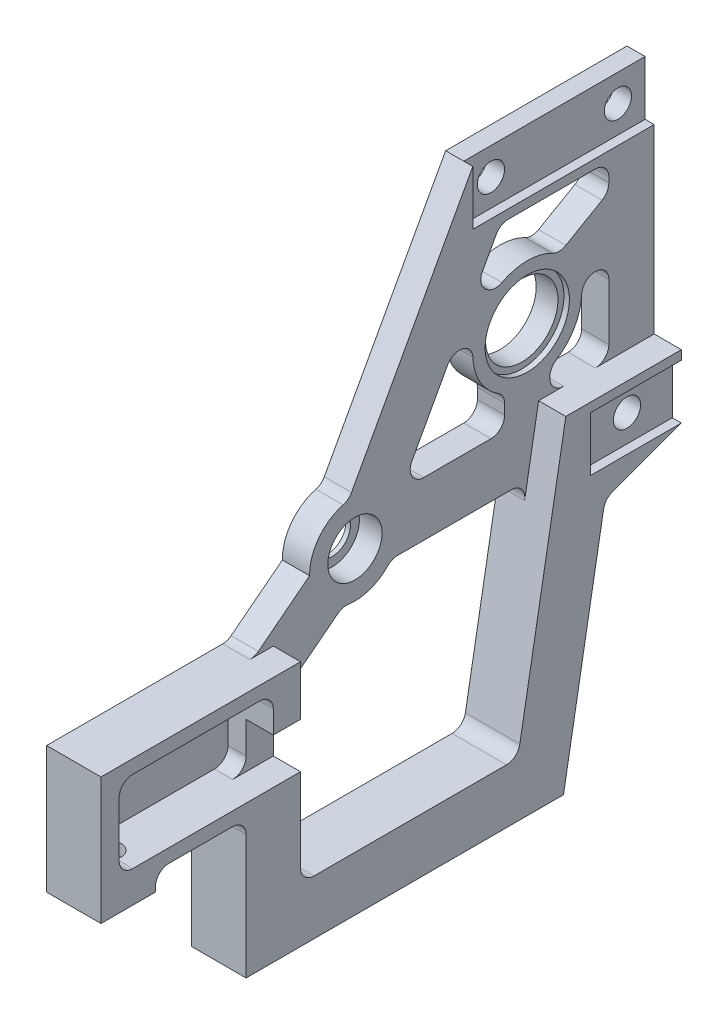
SolidWorks part; units mm, degrees
material "1060 Alloy"
ref_plane "Front Plane" through (0, 0, 0) normal (0, 0, 1) x (1, 0, 0)
ref_plane "Top Plane" through (0, 0, 0) normal (0, 1, 0) x (1, 0, 0)
ref_plane "Right Plane" through (0, 0, 0) normal (1, 0, 0) x (0, 0, -1)
sketch "Sketch1" plane through (0, 0, 0) normal (1, 0, 0) x (0, 0, -1)
  line L0 (51, 0) -> (55.5726, 25.9327)
  line L1 (16, 0) -> (51, 0)
  line L2 (0, 13.2) -> (0, 27.2)
  line L3 (44, 62) -> (64, 62)
  line L4 (64, 29) -> (64, 62)
  line L5 (55.5726, 25.9327) -> (64, 29)
  line L6 (16, 0) -> (16, 15.2)
  line L7 (16, 15.2) -> (6, 15.2)
  line L8 (0, 27.2) -> (19.9415, 27.2)
  line L9 (44, 62) -> (30.2889, 36.9492)
  line L10 (44, 62) -> (44, 56) construction
  line L11 (44, 56) -> (64, 56) construction
  line L12 (64, 29) -> (54, 29) construction
  line L13 (54, 29) -> (54, 35) construction
  line L14 (54, 35) -> (64, 35) construction
  line L15 (31, 32) -> (44, 55.7516) construction
  line L16 (41.9513, 45.7601) -> (36.062, 35)
  line L17 (31, 32) -> (59, 32) construction
  line L18 (50, 44) -> (58.0527, 48.6492) construction
  line L19 (41.9513, 45.7601) -> (44.0264, 44.5621)
  line L20 (47.0086, 55) -> (44.3526, 50.1473)
  line L21 (44.3526, 50.1473) -> (46.5264, 48.8922)
  line L22 (50, 44) -> (50, 36.0123) construction
  line L23 (59, 52.0829) -> (59, 55)
  line L24 (59, 55) -> (47.0086, 55)
  line L25 (31, 32) -> (19.9305, 23.391) construction
  line L26 (59, 46.3094) -> (59, 36)
  line L27 (59, 36) -> (52.5, 36)
  line L28 (52.5, 36) -> (52.5, 38.5456)
  line L29 (47.5, 35) -> (36.062, 35)
  line L30 (35, 29) -> (50.0209, 29)
  line L31 (22, 21.2) -> (29.6843, 27.1762)
  line L32 (50.0209, 29) -> (45.9654, 6)
  line L33 (45.9654, 6) -> (22, 6)
  line L34 (22, 6) -> (22, 21.2)
  line L35 (6, 15.2) -> (6, 13.2)
  line L36 (26.0008, 31.9125) -> (19.9415, 27.2)
  line L37 (6, 13.2) -> (0, 13.2)
  line L38 (47.5, 35) -> (47.5, 38.5456)
  line L40 (59, 52.0829) -> (53.4736, 48.8922)
  line L41 (59, 46.3094) -> (55.9736, 44.5621)
  line L42 (50, 44) -> (37.9544, 50.9545) construction
  circle A0 centre (59, 32) radius 1.5
  circle A1 centre (50, 44) radius 3.99
  circle A2 centre (61, 59) radius 1.5
  circle A3 centre (47, 59) radius 1.5
  circle A4 centre (31, 32) radius 2
  circle A5 centre (31, 32) radius 5 construction
  arc A6 (46.5264, 48.8922) -> (53.4736, 48.8922) centre (50, 44) cw
  arc A7 (52.5, 38.5456) -> (55.9736, 44.5621) centre (50, 44) ccw
  arc A8 (29.6843, 27.1762) -> (35, 29) centre (31, 32) ccw
  arc A9 (30.2889, 36.9492) -> (26.0008, 31.9125) centre (31, 32) ccw
  arc A11 (44.0264, 44.5621) -> (47.5, 38.5456) centre (50, 44) ccw
  dimension "D1" = 7.98
  dimension "D2" = 16
  dimension "D4" = 3
  dimension "D14" = 4
  dimension "D24" = 10
  dimension "D27" = 6
  dimension "D3" = 15.2
  dimension "D5" = 44
  dimension "D6" = 50
  dimension "D7" = 64
  dimension "D8" = 62
  dimension "D9" = 3
  dimension "D10" = 14
  dimension "D11" = 3
  dimension "D12" = 3
  dimension "D13" = 5
  dimension "D15" = 12
  dimension "D16" = 32
  dimension "D17" = 31
  dimension "D18" = 32
  dimension "D19" = 6
  dimension "D20" = 20
  dimension "D21" = 10
  dimension "D22" = 6
  dimension "D23" = 51
  dimension "D25" = 6
  dimension "D26" = 3
  dimension "D28" = 5
  dimension "D29" = 2.5
  dimension "D30" = 5
  dimension "D31" = 6
  dimension "D32" = 3
  dimension "D33" = 1
  dimension "D34" = 120
  dimension "D35" = 1
  dimension "D36" = 6
  dimension "D37" = 6
  dimension "D38" = 20
  dimension "D39" = 100
  dimension "D40" = 6
  dimension "D41" = 6
  dimension "D42" = 120
  dimension "D43" = 2.5
  dimension "D44" = 2.5
  dimension "D45" = 2.5
  dimension "D46" = 2.5
  dimension "D47" = 3
  dimension "D48" = 3
  dimension "D49" = 2
  dimension "D50" = 6
extrude "Boss-Extrude1" add sketch "Sketch1" along normal blind 6
hole_wizard "Tap Drill for M3 Tap1" positions "Sketch5" profile "Sketch4" hole size "M3" standard "ISO"
sketch "Sketch5" plane through (0, 0, 0) normal (0, -1, 0) x (-1, 0, 0)
  line L0 (0, 16) -> (0, 51) construction
  line L2 (-6, 51) -> (0, 51) construction
  line L4 (-6, 16) -> (0, 16) construction
  point P0 (-3, 48)
  point P2 (-3, 19)
  dimension "D1" = 3
  dimension "D2" = 3
  dimension "D3" = 3
sketch "Sketch4" plane through (3, 0, -48) normal (1, 0, 0) x (0, 0, -1)
  line L0 (0, 0) -> (0, 9.7511)
  line L1 (0, 9.7511) -> (1.25, 9)
  line L2 (1.25, 9) -> (1.25, 0)
  line L5 (1.25, 0) -> (0, 0)
  line L10 (0, 9.7511) -> (-1.25, 9) construction
  line L11 (0, -6.35) -> (0, 107.95) construction
  dimension "Hole Dia." = 2.5
  dimension "Hole Depth" = 9
  dimension "Drill Angle" = 118
sketch "Sketch13" plane through (6, 0, 0) normal (1, 0, 0) x (0, 0, -1)
  line L0 (64, 29) -> (64, 62) construction
  line L1 (51.2552, 36) -> (64, 36)
  line L2 (64, 62) -> (44, 62) construction
  line L3 (64, 62) -> (44, 62)
  line L4 (64, 36) -> (64, 62)
  line L5 (30.2889, 36.9492) -> (19.9415, 36.9492)
  line L6 (22, 21.2) -> (22, 6) construction
  line L10 (29.6843, 27.1762) -> (22, 21.2) construction
  line L11 (44, 62) -> (30.2889, 36.9492)
  line L12 (22, 21.2) -> (50.0209, 29)
  line L13 (44, 62) -> (30.2889, 36.9492) construction
  line L14 (50.0209, 29) -> (51.2552, 36)
  line L20 (22, 21.2) -> (22, 27.2)
  line L21 (22, 27.2) -> (19.9415, 27.2)
  line L22 (19.9415, 27.2) -> (0, 27.2) construction
  line L23 (19.9415, 27.2) -> (19.9415, 36.9492)
  line L24 (45.9654, 6) -> (50.0209, 29) construction
  arc A2 (30.2889, 36.9492) -> (26.0008, 31.9125) centre (31, 32) ccw construction
  dimension "D3" = 26
extrude "Cut-Extrude4" cut sketch "Sketch13" against normal blind 3
sketch "Sketch14" plane through (3, 0, 0) normal (1, 0, 0) x (0, 0, -1)
  line L1 (64, 62) -> (44, 62)
  line L2 (64, 62) -> (64, 56)
  line L3 (64, 56) -> (44, 56)
  line L4 (44, 62) -> (44, 56)
  dimension "D1" = 6
extrude "Cut-Extrude5" cut sketch "Sketch14" against normal blind 1
sketch "Sketch15" plane through (6, 0, 0) normal (1, 0, 0) x (0, 0, -1)
  line L1 (64, 29) -> (54, 29)
  line L2 (64, 29) -> (64, 35)
  line L3 (64, 35) -> (54, 35)
  line L4 (54, 29) -> (54, 35)
  dimension "D1" = 10
  dimension "D2" = 6
extrude "Cut-Extrude6" cut sketch "Sketch15" against normal blind 1
sketch "Sketch16" plane through (3, 0, 0) normal (1, 0, 0) x (0, 0, -1)
  circle A0 centre (31, 32) radius 2.99
  dimension "D1" = 5.98
extrude "Cut-Extrude7" cut sketch "Sketch16" against normal blind 2.5
sketch "Sketch17" plane through (6, 0, 0) normal (1, 0, 0) x (0, 0, -1)
  line L0 (0, 27.2) -> (0, 13.2) construction
  line L1 (2, 25.7) -> (19, 25.7)
  line L2 (2, 25.7) -> (2, 16.7)
  line L3 (2, 16.7) -> (19, 16.7)
  line L4 (19, 25.7) -> (19, 16.7)
  line L5 (22, 27.2) -> (0, 27.2) construction
  line L6 (6, 15.2) -> (16, 15.2) construction
  line L7 (22, 27.2) -> (22, 6) construction
  dimension "D1" = 2
  dimension "D2" = 1.5
  dimension "D3" = 1.5
  dimension "D4" = 3
extrude "Cut-Extrude8" cut sketch "Sketch17" against normal offset from surface (5 mm away) 1 up to face at (0, 40.1727, -55.9866)
fillet "Fillet1" radius 1.5 4 edges at (3.5, 25.7, -2) (3.5, 16.7, -2) (3.5, 16.7, -19) (3.5, 25.7, -19)
sketch "Sketch18" plane through (1, 0, 0) normal (1, 0, 0) x (0, 0, -1)
  line L0 (5, 23.7) -> (16.5, 23.7) construction
  line L1 (5, 25.2) -> (16.5, 25.2)
  line L2 (5, 22.2) -> (16.5, 22.2)
  line L3 (17.5, 25.7) -> (3.5, 25.7) construction
  line L4 (2, 24.2) -> (2, 18.2) construction
  line L5 (19, 18.2) -> (19, 24.2) construction
  arc A0 (5, 25.2) -> (5, 22.2) centre (5, 23.7) ccw
  arc A1 (16.5, 22.2) -> (16.5, 25.2) centre (16.5, 23.7) ccw
  point P2 (10.75, 23.7)
  dimension "D1" = 3
  dimension "D2" = 2
  dimension "D3" = 3
  dimension "D4" = 2.5
extrude "Cut-Extrude9" cut sketch "Sketch18" against normal up to next
sketch "Sketch19" plane through (6, 0, 0) normal (1, 0, 0) x (0, 0, -1)
  line L0 (22, 27.2) -> (22, 6) construction
  line L1 (22, 21.7) -> (17.5, 21.7)
  line L2 (22, 21.7) -> (22, 16.7)
  line L3 (22, 16.7) -> (17.5, 16.7)
  line L4 (17.5, 21.7) -> (17.5, 16.7)
  dimension "D1" = 5
extrude "Cut-Extrude10" cut sketch "Sketch19" against normal blind 3
sketch "Sketch20" plane through (3, 0, 0) normal (1, 0, 0) x (0, 0, -1)
  circle A0 centre (50, 44) radius 4.65
  dimension "D1" = 9.3
extrude "Cut-Extrude11" cut sketch "Sketch20" against normal blind 0.6
fillet "Fillet2" radius 1.5 16 edges at (1.5, 55, -47.0086) (1.5, 50.1473, -44.3526) (1.5, 48.8922, -46.5264) (1.5, 48.8922, -53.4736) (1.5, 55, -59) (1.5, 52.0829, -59) (1.5, 44.5621, -55.9736) (1.5, 46.3094, -59) (1.5, 38.5456, -52.5) (1.5, 36, -52.5) (1.5, 36, -59) (1.5, 35, -36.062) (1.5, 35, -47.5) (1.5, 38.5456, -47.5) (1.5, 45.7601, -41.9513) (1.5, 44.5621, -44.0264)
fillet "Fillet3" radius 1.5 11 edges at (1.5, 29, -50.0209) (3, 6, -45.9654) (3, 6, -22) (1.5, 29, -35) (1.5, 27.1762, -29.6843) (1.5, 27.2, -19.9415) (1.5, 36.9492, -30.2889) (3, 15.2, -16) (1.5, 21.2, -22) (3, 15.2, -6) (3, 25.9327, -55.5726)
hole_wizard "Tap Drill for M3 Tap2" positions "Sketch22" profile "Sketch21" hole size "M3" standard "ISO" end condition up to next
sketch "Sketch22" plane through (0, 13.2, 0) normal (0, -1, 0) x (-1, 0, 0)
  line L0 (-6, 0) -> (0, 0) construction
  line L1 (0, 7.5) -> (0, 14.5) construction
  point P0 (-3, 4)
  dimension "D1" = 4
  dimension "D2" = 3
sketch "Sketch21" plane through (3, 13.2, -4) normal (1, 0, 0) x (0, 0, -1)
  line L0 (0, 0) -> (0, 3.5)
  line L1 (0, 3.5) -> (1.25, 3.5)
  line L2 (1.25, 3.5) -> (1.25, 0)
  line L5 (1.25, 0) -> (0, 0)
  line L11 (0, -6.35) -> (0, 107.95) construction
  dimension "Thru Hole Dia." = 2.5
  dimension "Thru Hole Depth" = 3.5
